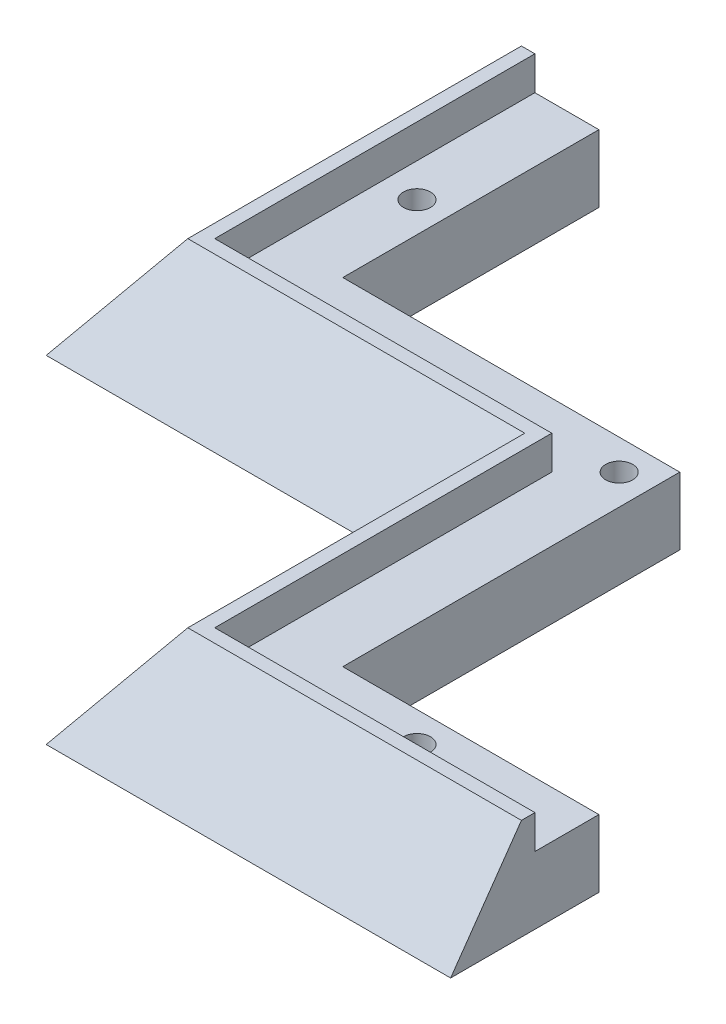
SolidWorks part; units mm, degrees
ref_plane "Plan de face" through (0, 0, 0) normal (0, 0, 1) x (1, 0, 0)
ref_plane "Plan de dessus" through (0, 0, 0) normal (0, 1, 0) x (1, 0, 0)
ref_plane "Plan de droite" through (0, 0, 0) normal (1, 0, 0) x (0, 0, -1)
sketch "Esquisse1" plane through (0, 0, 0) normal (0, 1, 0) x (1, 0, 0)
  line L0 (-41.3523, -18.6477) -> (8.6477, -18.6477)
  line L1 (68.6477, -68.6477) -> (8.6477, -68.6477)
  line L2 (68.6477, -68.6477) -> (68.6477, -46.6477)
  line L3 (-19.3523, 41.3523) -> (-41.3523, 41.3523)
  line L4 (-41.3523, -18.6477) -> (-41.3523, 41.3523)
  line L5 (68.6477, -68.6477) -> (-41.3523, 41.3523) construction
  line L6 (55, 80) -> (-55, -80) construction
  line L7 (8.6477, -18.6477) -> (8.6477, -68.6477)
  line L8 (-19.3523, 41.3523) -> (-19.3523, 3.3523)
  line L9 (-19.3523, 3.3523) -> (30.6477, 3.3523)
  line L10 (30.6477, 3.3523) -> (30.6477, -46.6477)
  line L11 (30.6477, -46.6477) -> (68.6477, -46.6477)
  point P0 (0, 0)
  dimension "D1" = 110
  dimension "D2" = 110
  dimension "D3" = 50
  dimension "D4" = 22
  dimension "D5" = 22
  dimension "D6" = 22
  dimension "D7" = 22
extrude "Boss.-Extru.1" add sketch "Esquisse1" along normal blind 15
chamfer "Chanfrein1" distance 15 angle 35 4 edges at (38.6477, 15, 68.6477) (8.6477, 15, 43.6477) (-16.3523, 15, 18.6477) (-41.3523, 15, -11.3523) first distance on face at (38.6477, 7.5, 68.6477) first distance on face at (8.6477, 7.5, 43.6477) first distance on face at (-16.3523, 7.5, 18.6477) first distance on face at (-41.3523, 7.5, -11.3523)
sketch "Esquisse4" plane through (0, 0, 0) normal (0, -1, 0) x (1, 0, 0)
  line L0 (-36.3523, -36.3523) -> (-36.3523, 13.6477) construction
  line L1 (-19.3523, -41.3523) -> (-41.3523, -41.3523) construction
  line L2 (-41.3523, 18.6477) -> (8.6477, 18.6477) construction
  line L3 (-36.3523, 13.6477) -> (13.6477, 13.6477) construction
  line L4 (-41.3523, -41.3523) -> (-41.3523, 18.6477) construction
  line L6 (63.6477, 63.6477) -> (13.6477, 63.6477) construction
  line L7 (68.6477, 68.6477) -> (68.6477, 46.6477) construction
  line L8 (8.6477, 18.6477) -> (8.6477, 68.6477) construction
  line L9 (13.6477, 63.6477) -> (13.6477, 13.6477) construction
  line L10 (8.6477, 68.6477) -> (68.6477, 68.6477) construction
  line L12 (-19.3523, -36.3523) -> (-36.3523, -36.3523) construction
  line L13 (-19.3523, -3.3523) -> (-19.3523, -41.3523) construction
  line L14 (63.6477, 46.6477) -> (63.6477, 63.6477) construction
  line L15 (68.6477, 46.6477) -> (30.6477, 46.6477) construction
  circle A0 centre (38.6477, 63.6477) radius 2
  circle A1 centre (13.6477, 38.6477) radius 2
  circle A2 centre (-11.3523, 13.6477) radius 2
  dimension "D7" = 4
  dimension "D1" = 5
  dimension "D2" = 5
  dimension "D3" = 5
  dimension "D4" = 5
  dimension "D5" = 5
  dimension "D6" = 5
extrude "Enlèv. mat.-Extru.3" cut sketch "Esquisse4" against normal blind 4
sketch "Esquisse5" plane through (0, 15, 0) normal (0, 1, 0) x (1, 0, 0)
  line L0 (-28.8492, 41.3523) -> (-19.3523, 41.3523)
  line L1 (-19.3523, 41.3523) -> (-30.8492, 41.3523) construction
  line L2 (-19.3523, 41.3523) -> (-19.3523, 3.3523)
  line L3 (-19.3523, 3.3523) -> (30.6477, 3.3523)
  line L4 (30.6477, 3.3523) -> (30.6477, -46.6477)
  line L5 (30.6477, -46.6477) -> (68.6477, -46.6477)
  line L6 (68.6477, -46.6477) -> (68.6477, -56.1404)
  line L7 (68.6477, -58.1445) -> (68.6477, -46.6477) construction
  line L8 (68.6477, -56.1404) -> (21.1508, -56.1404)
  line L9 (21.1508, -56.1404) -> (21.1508, -6.1445)
  line L10 (21.1508, -6.1445) -> (-28.8492, -6.1445)
  line L11 (-28.8492, -6.1445) -> (-28.8492, 41.3523)
  line L12 (-30.8492, 41.3523) -> (-30.8492, -8.1445) construction
  line L13 (19.1508, -58.1445) -> (68.6477, -58.1445) construction
  line L14 (-30.8492, -8.1445) -> (19.1508, -8.1445) construction
  line L15 (19.1508, -8.1445) -> (19.1508, -58.1445) construction
  dimension "D1" = 2
  dimension "D2" = 2.0042
  dimension "D3" = 2
  dimension "D4" = 2
extrude "Enlèv. mat.-Extru.5" cut sketch "Esquisse5" against normal blind 5
sketch "Esquisse6" plane through (0, 10, 0) normal (0, 1, 0) x (1, 0, 0)
  line L0 (-23.8492, 41.3523) -> (-23.8492, -1.1445) construction
  line L1 (-19.3523, 41.3523) -> (-28.8492, 41.3523) construction
  line L2 (-23.8492, -1.1445) -> (26.1508, -1.1445) construction
  line L3 (26.1508, -1.1445) -> (26.1508, -51.1404) construction
  line L4 (26.1508, -51.1404) -> (68.6477, -51.1404) construction
  line L5 (68.6477, -56.1404) -> (68.6477, -46.6477) construction
  line L6 (-28.8492, 41.3523) -> (-28.8492, -6.1445) construction
  line L7 (-28.8492, -6.1445) -> (21.1508, -6.1445) construction
  line L8 (21.1508, -6.1445) -> (21.1508, -56.1404) construction
  line L9 (21.1508, -56.1404) -> (68.6477, -56.1404) construction
  circle A0 centre (-23.8492, 18.8555) radius 2
  circle A1 centre (26.1508, -1.1445) radius 2
  circle A2 centre (46.1508, -51.1404) radius 2
  dimension "D5" = 4
  dimension "D1" = 5
  dimension "D2" = 5
  dimension "D3" = 5
  dimension "D4" = 5
  dimension "D6" = 20
  dimension "D7" = 20
extrude "Enlèv. mat.-Extru.6" cut sketch "Esquisse6" against normal blind 5
